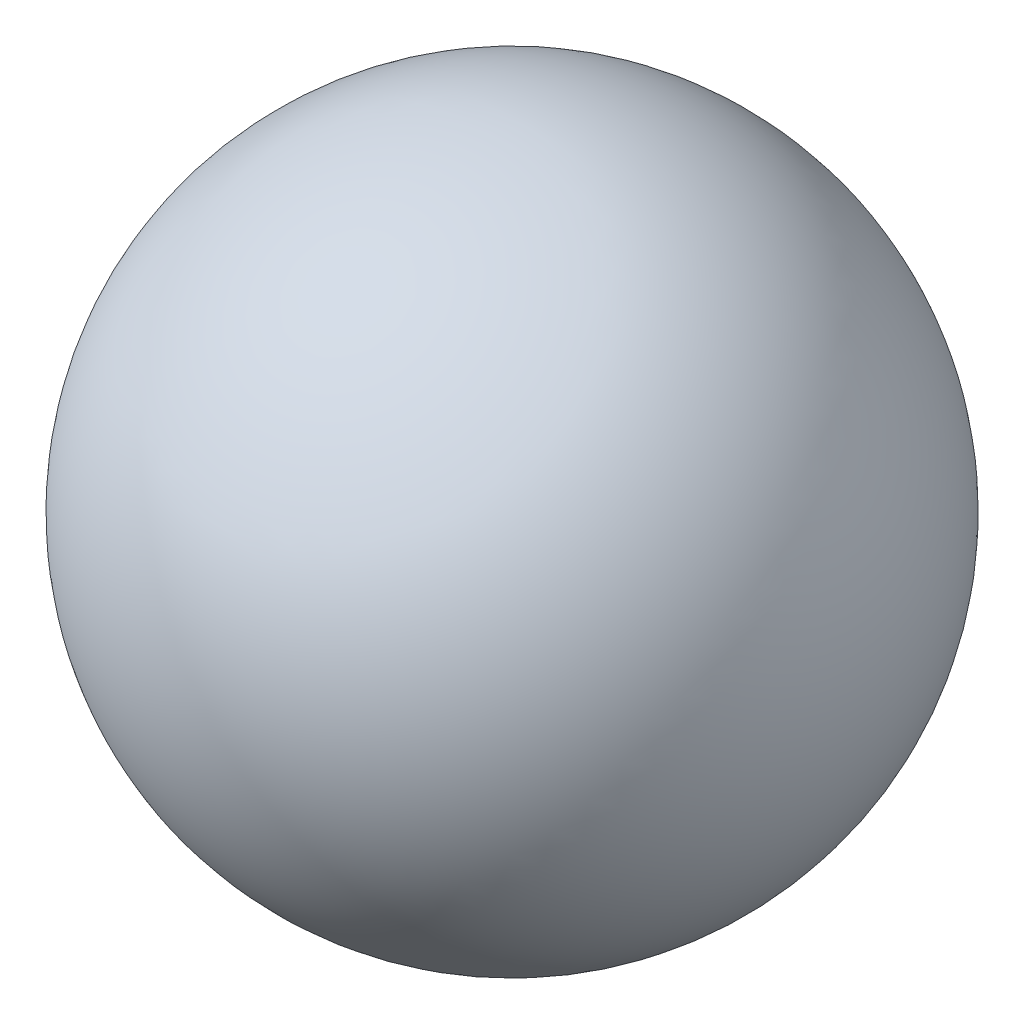
SolidWorks part; units mm, degrees
material "Plain Carbon Steel"
ref_plane "Front Plane" through (0, 0, 0) normal (0, 0, 1) x (1, 0, 0)
ref_plane "Top Plane" through (0, 0, 0) normal (0, 1, 0) x (1, 0, 0)
ref_plane "Right Plane" through (0, 0, 0) normal (1, 0, 0) x (0, 0, -1)
sketch "Sketch1" plane through (0, 0, 0) normal (1, 0, 0) x (0, 0, -1)
  line L0 (0, 0) -> (-14.2498, 0) construction
  line L1 (0, 0) -> (26.2357, 0) construction
  line L2 (-2.5, 0) -> (2.5, 0)
  arc A0 (2.5, 0) -> (-2.5, 0) centre (0, 0) ccw
  dimension "D1" = 5
revolve "Revolve1" add sketch "Sketch1" angle 360 about L0
ref_axis "Axis1" through (0, 0, 16.2741) along (0, 0, -1)
